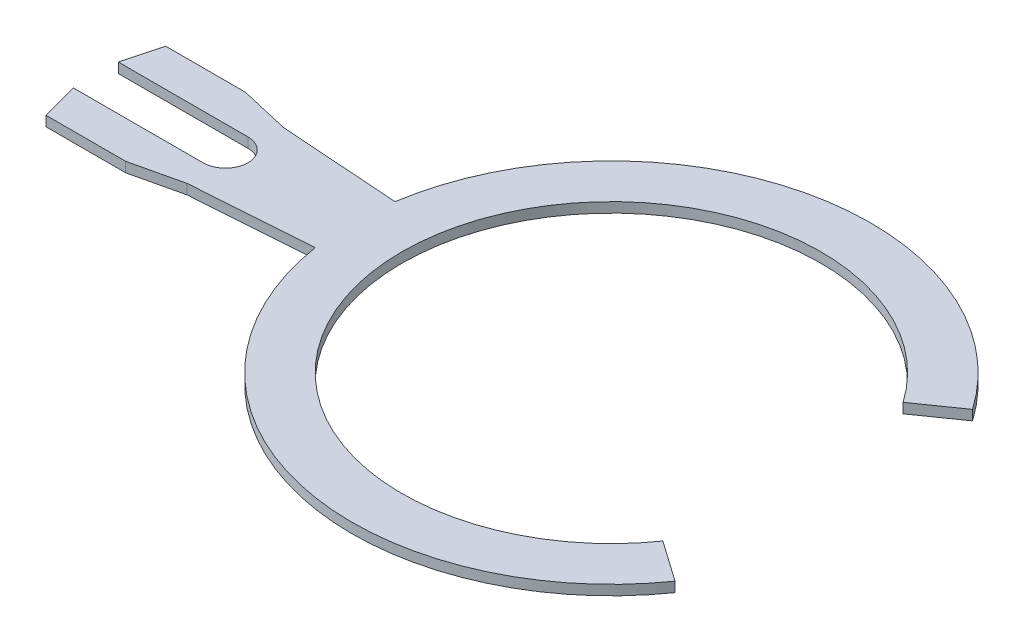
SolidWorks part; units mm, degrees
ref_plane "Alzado" through (0, 0, 0) normal (0, 0, 1) x (1, 0, 0)
ref_plane "Planta" through (0, 0, 0) normal (0, 1, 0) x (1, 0, 0)
ref_plane "Vista lateral" through (0, 0, 0) normal (1, 0, 0) x (0, 0, -1)
ref_plane "Plane1" through (0, -0.2, 0) normal (0, -1, 0) x (1, 0, 0)
sketch "Sketch1" plane through (0, -0.2, 0) normal (0, -1, 0) x (1, 0, 0)
  line L0 (1.7202, 1.2045) -> (2.1298, 1.4913)
  line L1 (-2.569, 0.4) -> (-3.769, 0.4839)
  line L2 (-3.769, 0.4839) -> (-4.269, 0.6)
  line L3 (-4.269, 0.6) -> (-5.0686, 0.6)
  line L4 (-5.0686, 0.6) -> (-5.169, 0.225)
  line L5 (-5.169, 0.225) -> (-3.869, 0.225)
  line L6 (-3.869, -0.225) -> (-5.169, -0.225)
  line L7 (-5.169, -0.225) -> (-5.0686, -0.6)
  line L8 (-5.0686, -0.6) -> (-4.269, -0.6)
  line L9 (-4.269, -0.6) -> (-3.769, -0.4839)
  line L10 (-3.769, -0.4839) -> (-2.569, -0.4)
  line L11 (2.1298, -1.4913) -> (1.7202, -1.2045)
  line L12 (0, 0) -> (1.7202, 1.2045) construction
  line L13 (0, 0) -> (1.7202, -1.2045) construction
  arc A0 (2.1298, 1.4913) -> (-2.569, 0.4) centre (0, 0) ccw
  arc A1 (-3.869, 0.225) -> (-3.869, -0.225) centre (-3.869, 0) cw
  arc A2 (-2.569, -0.4) -> (2.1298, -1.4913) centre (0, 0) ccw
  arc A3 (1.7202, -1.2045) -> (1.7202, 1.2045) centre (0, 0) cw
  dimension "D1" = 2.6
  dimension "D2" = 0.225
  dimension "D3" = 2.6
  dimension "D4" = 2.1
  dimension "D5" = 70
  dimension "D6" = 3.869
  dimension "D7" = 1.2
  dimension "D8" = 0.45
  dimension "D9" = 0.9678
  dimension "D10" = 0.8
  dimension "D11" = 3.769
  dimension "D12" = 4.269
extrude "Boss-Extrude1" add sketch "Sketch1" against normal blind 0.1
sketch "Sketch3" plane through (0, 0, 0) normal (0, 1, 0) x (1, 0, 0)
  line L0 (0, 0) -> (-6.09, 0) construction
  line L1 (-3.644, 0) -> (-5.248, 0)
  arc A0 (-3.869, -0.225) -> (-3.869, 0.225) centre (-3.869, 0) ccw construction
  arc A1 (-3.869, -0.225) -> (-3.869, 0.225) centre (-3.869, 0) ccw construction
  point P6 (-3.644, 0)
ref_axis "Axis1" through (-3.644, 0, 0) along (-1, 0, 0)
